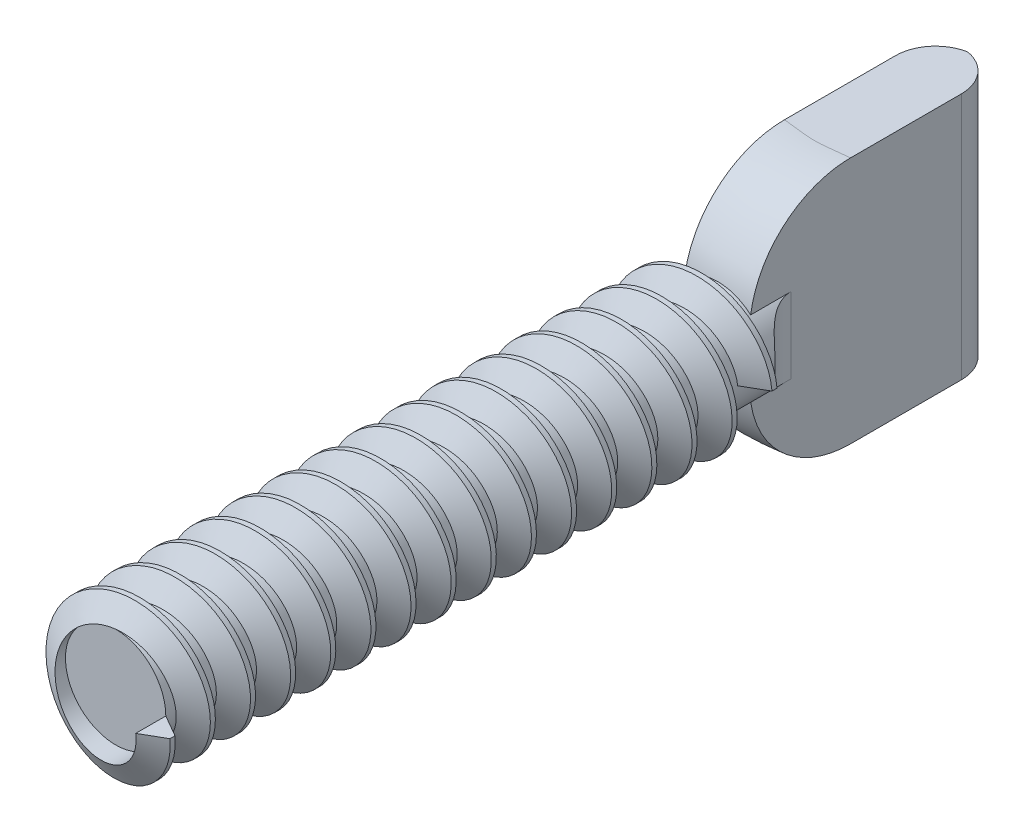
SolidWorks part; units mm, degrees
ref_plane "Front Plane" through (0, 0, 0) normal (0, 0, 1) x (1, 0, 0)
ref_plane "Top Plane" through (0, 0, 0) normal (0, 1, 0) x (1, 0, 0)
ref_plane "Right Plane" through (0, 0, 0) normal (1, 0, 0) x (0, 0, -1)
sketch "Sketch1" plane through (0, 0, 0) normal (0, 0, 1) x (1, 0, 0)
  circle A0 centre (0, 0) radius 1
  dimension "D1" = 2
extrude "Boss-Extrude1" add sketch "Sketch1" along normal blind 12
sketch "Sketch2" plane through (0, 0, 0) normal (0, 0, -1) x (-1, 0, 0)
  line L1 (-0.6583, -2.4685) -> (0.6583, -2.4685)
  line L2 (-0.6583, -2.4685) -> (-0.6583, 2.4685)
  line L3 (-0.6583, 2.4685) -> (0.6583, 2.4685)
  line L4 (0.6583, -2.4685) -> (0.6583, 2.4685)
  line L5 (-0.6583, -2.4685) -> (0.6583, 2.4685) construction
  line L6 (-0.6583, 2.4685) -> (0.6583, -2.4685) construction
  point P0 (0, 0)
  point P8 (0, 0)
  point P9 (0, 0)
extrude "Boss-Extrude2" add sketch "Sketch2" along normal blind 5
fillet "Fillet1" radius 2 2 edges at (0, -2.4685, 0) (0, 2.4685, 0)
fillet "Fillet2" radius 0.8 4 edges at (0.6583, 0, -5) (-0.6583, 0, -5) (-0.6583, 0, 0) (0.6583, 0, 0)
thread "Thread1" pitch 0.8 method extrude profile "Thread Profile1" start angle 0, offset 0, length 0, pitch 0.8, diameter 2
ref_plane "Plane1" through (1, 0, 0) normal (0, -1, 0) x (1, 0, 0)
sketch "Thread Profile1" plane through (1, 0, 0) normal (0, -1, 0) x (1, 0, 0)
  line L0 (0, 0) -> (0, 0.8) construction
  line L1 (0, 0) -> (0.433, 0.25)
  line L2 (0.433, 0.25) -> (0.433, 0.35)
  line L3 (0.433, 0.35) -> (0, 0.6)
  line L4 (0.433, 0.3) -> (0, 0.3) construction
  line L11 (0, 0) -> (0, 0.6)
  point P2 (0, 0)
  dimension "Pitch" = 0.8
  dimension "Profile_Angle" = 60
  dimension "Profile_Land" = 0.1
  dimension "Profile_Height" = 0.433
